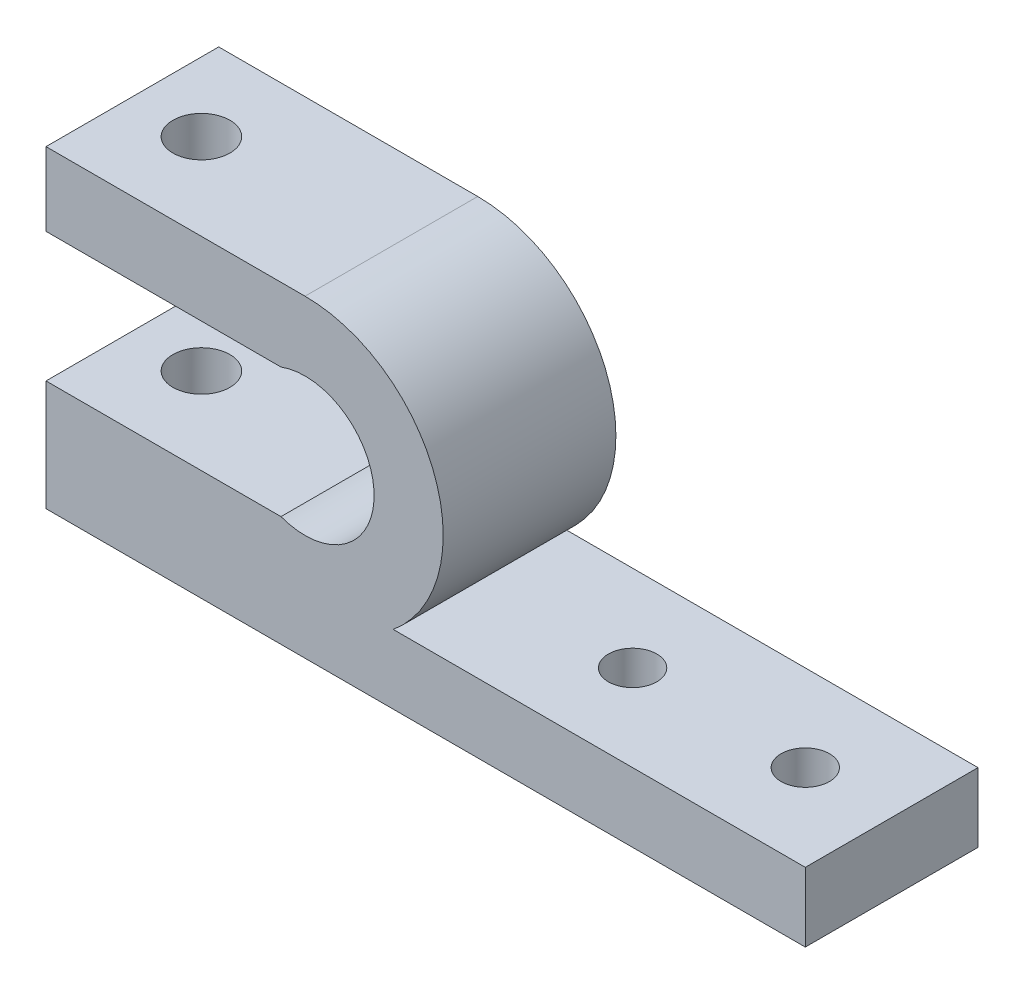
SolidWorks part; units mm, degrees
ref_plane "Front Plane" through (0, 0, 0) normal (0, 0, 1) x (1, 0, 0)
ref_plane "Top Plane" through (0, 0, 0) normal (0, 1, 0) x (1, 0, 0)
ref_plane "Right Plane" through (0, 0, 0) normal (1, 0, 0) x (0, 0, -1)
sketch "Sketch1" plane through (0, 0, 0) normal (0, 0, 1) x (1, 0, 0)
  line L0 (10.2878, 23.8568) -> (-3.3203, 23.8568)
  line L1 (10.2878, 16.3568) -> (-3.3203, 16.3568)
  line L2 (11.6797, 12.1068) -> (-3.3203, 12.1068)
  line L3 (-3.3203, 12.1068) -> (-3.3203, 16.3568)
  line L4 (11.6797, 28.1068) -> (-3.3203, 28.1068)
  line L5 (-3.3203, 28.1068) -> (-3.3203, 23.8568)
  circle A1 centre (27.6472, 16.9489) radius 1.65 construction
  arc A2 (11.6797, 12.1068) -> (11.6797, 28.1068) centre (11.6797, 20.1068) ccw
  circle A3 centre (27.6472, 16.9489) radius 1.65
  arc A4 (10.2878, 16.3568) -> (10.2878, 23.8568) centre (11.6797, 20.1068) ccw
  circle A5 centre (11.6797, 20.1068) radius 4 construction
  dimension "D1" = 8
  dimension "D2" = 16
  dimension "D4" = 15
  dimension "D3" = 7.5
  dimension "D5" = 15
extrude "Boss-Extrude1" add sketch "Sketch1" along normal blind 10 contours L4 L5 L0 A4 L1 L3 L2 A2
sketch "Sketch2" plane through (0, 28.1068, 0) normal (0, 1, 0) x (1, 0, 0)
  line L0 (-3.3203, -10) -> (-3.3203, 0) construction
  line L1 (11.6797, -10) -> (-3.3203, -10) construction
  circle A0 centre (0.6797, -5) radius 1.65
  dimension "D1" = 3.3
  dimension "D2" = 4
extrude "Cut-Extrude1" cut sketch "Sketch2" against normal through all
ref_plane "Plane1" through (40.6472, 13.9489, 10) normal (1, 0, 0) x (0, 0, -1)
sketch "Sketch5" plane through (0, 0, 10) normal (0, 0, 1) x (1, 0, 0)
  line L0 (20.6472, 13.9489) -> (40.6472, 13.9489) construction
  line L1 (20.6472, 13.9489) -> (40.6472, 13.9489)
  line L2 (40.6472, 13.9489) -> (40.6472, 9.9489)
  line L3 (40.6472, 9.9489) -> (-3.3203, 9.9489)
  line L4 (-3.3203, 12.1068) -> (-3.3203, 9.9489)
  line L5 (11.6797, 12.1068) -> (-3.3203, 12.1068) construction
  line L6 (11.6797, 12.1068) -> (-3.3203, 12.1068)
  line L7 (20.6472, 13.9489) -> (16.7866, 13.9489)
  arc A0 (11.6797, 12.1068) -> (11.6797, 28.1068) centre (11.6797, 20.1068) ccw construction
  arc A1 (11.6797, 12.1068) -> (16.7866, 13.9489) centre (11.6797, 20.1068) ccw
  dimension "D1" = 4
extrude "Boss-Extrude2" add sketch "Sketch5" against normal blind 10 contours L1 L2 L3 L4 L6 A1 L7
sketch "Sketch6" plane through (0, 12.1068, 0) normal (0, 1, 0) x (1, 0, 0)
  circle A1 centre (0.6797, -5) radius 1.65
  circle A2 centre (0.6797, -5) radius 1.65
  dimension "D1" = 0
extrude "Cut-Extrude2" cut sketch "Sketch6" against normal through all
sketch "Sketch8" plane through (0, 13.9489, 0) normal (0, 1, 0) x (1, 0, 0)
  line L0 (16.7866, -10) -> (40.6472, -10) construction
  circle A0 centre (25.6472, -7.5) radius 1.25 construction
  circle A1 centre (25.6472, -7.5) radius 1.25 construction
  circle A2 centre (35.6472, -7.5) radius 1.25 construction
  circle A3 centre (35.6472, -7.5) radius 1.25 construction
  circle A4 centre (25.6472, -5) radius 1.4
  circle A5 centre (35.6472, -5) radius 1.4
  dimension "D1" = 2.8
  dimension "D2" = 2.8
  dimension "D3" = 5
  dimension "D4" = 5
extrude "Cut-Extrude3" cut sketch "Sketch8" against normal blind 10 contours A4 | A5
